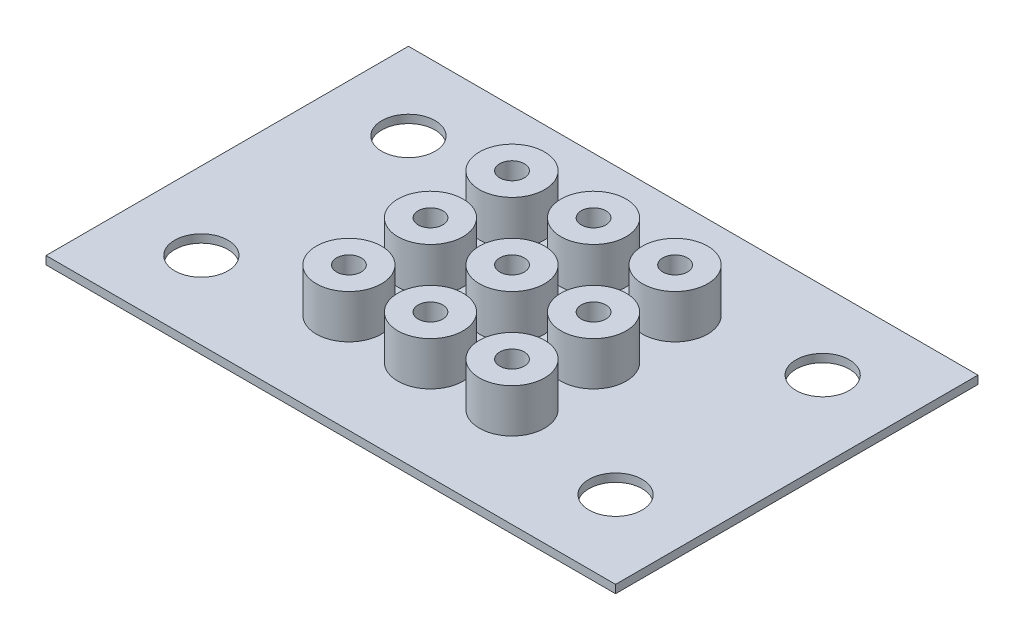
SolidWorks part; units mm, degrees
ref_plane "Front Plane" through (0, 0, 0) normal (0, 0, 1) x (1, 0, 0)
ref_plane "Top Plane" through (0, 0, 0) normal (0, 1, 0) x (1, 0, 0)
ref_plane "Right Plane" through (0, 0, 0) normal (1, 0, 0) x (0, 0, -1)
sketch "Sketch1" plane through (0, 0, 0) normal (0, 1, 0) x (1, 0, 0)
  line L0 (9.525, 34.925) -> (0, 34.925) construction
  line L1 (0, 0) -> (69.85, 0)
  line L2 (0, 0) -> (0, 44.45)
  line L3 (0, 44.45) -> (69.85, 44.45)
  line L4 (69.85, 0) -> (69.85, 44.45)
  line L5 (9.525, 34.925) -> (60.325, 34.925) construction
  line L6 (9.525, 34.925) -> (9.525, 9.525) construction
  line L7 (9.525, 9.525) -> (60.325, 9.525) construction
  line L8 (60.325, 34.925) -> (60.325, 9.525) construction
  line L9 (9.525, 34.925) -> (9.525, 44.45) construction
  line L10 (34.925, 22.225) -> (34.925, 32.225) construction
  circle A0 centre (9.525, 34.925) radius 3.2639
  circle A1 centre (60.325, 34.925) radius 3.2639
  circle A2 centre (9.525, 9.525) radius 3.2639
  circle A3 centre (60.325, 9.525) radius 3.2639
  circle A4 centre (34.925, 22.225) radius 1.25
  circle A5 centre (44.925, 22.225) radius 1.25
  circle A6 centre (44.925, 32.225) radius 1.25
  circle A7 centre (34.925, 32.225) radius 1.25
  circle A8 centre (24.925, 22.225) radius 1.25
  circle A9 centre (24.925, 32.225) radius 1.25
  circle A10 centre (34.925, 32.225) radius 1.25
  circle A11 centre (44.925, 22.225) radius 1.25
  circle A12 centre (44.925, 12.225) radius 1.25
  circle A13 centre (34.925, 12.225) radius 1.25
  circle A14 centre (24.925, 22.225) radius 1.25
  circle A15 centre (24.925, 12.225) radius 1.25
  circle A16 centre (34.925, 12.225) radius 1.25
  point P13 (34.925, 34.925)
  point P14 (34.925, 44.45)
  point P20 (69.85, 22.225)
  dimension "D5" = 6.5278
  dimension "D6" = 2.5
  dimension "D1" = 69.85
  dimension "D2" = 44.45
  dimension "D3" = 50.8
  dimension "D4" = 25.4
  dimension "D9" = 10
  dimension "D16" = 10
  dimension "D17" = 10
  dimension "D18" = 10
  dimension "D19" = 10
  dimension "D20" = 10
  dimension "D21" = 10
  dimension "D22" = 10
  dimension "D7" = 2
  dimension "D8" = 2
  dimension "D10" = 2
  dimension "D11" = 2
  dimension "D12" = 2
  dimension "D13" = 2
  dimension "D14" = 2
  dimension "D15" = 2
extrude "Boss-Extrude1" add sketch "Sketch1" along normal blind 1 contours L1 L4 L3 L2 A15 A13 A12 A9 A8 A7 A6 A5 A4 A3 A2 A1 A0 region at (0.8279, 0, -22.225)
sketch "Sketch2" plane through (0, 1, 0) normal (0, 1, 0) x (1, 0, 0)
  line L0 (34.925, 22.225) -> (34.925, 32.225) construction
  circle A0 centre (34.925, 22.225) radius 4
  circle A1 centre (34.925, 22.225) radius 1.51
  circle A2 centre (44.925, 22.225) radius 4
  circle A3 centre (44.925, 22.225) radius 1.51
  circle A4 centre (44.925, 32.225) radius 4
  circle A5 centre (44.925, 32.225) radius 1.51
  circle A6 centre (34.925, 32.225) radius 4
  circle A7 centre (34.925, 32.225) radius 1.51
  circle A8 centre (44.925, 22.225) radius 1.51
  circle A9 centre (44.925, 22.225) radius 4
  circle A10 centre (44.925, 12.225) radius 1.51
  circle A11 centre (44.925, 12.225) radius 4
  circle A12 centre (34.925, 12.225) radius 1.51
  circle A13 centre (34.925, 12.225) radius 4
  circle A14 centre (24.925, 22.225) radius 4
  circle A15 centre (24.925, 22.225) radius 1.51
  circle A16 centre (24.925, 32.225) radius 4
  circle A17 centre (24.925, 32.225) radius 1.51
  circle A18 centre (34.925, 32.225) radius 4
  circle A19 centre (34.925, 32.225) radius 1.51
  circle A20 centre (24.925, 22.225) radius 1.51
  circle A21 centre (24.925, 22.225) radius 4
  circle A22 centre (24.925, 12.225) radius 1.51
  circle A23 centre (24.925, 12.225) radius 4
  circle A24 centre (34.925, 12.225) radius 1.51
  circle A25 centre (34.925, 12.225) radius 4
  dimension "D1" = 3.02
  dimension "D2" = 8
  dimension "D5" = 10
  dimension "D10" = 10
  dimension "D11" = 10
  dimension "D12" = 10
  dimension "D13" = 10
  dimension "D14" = 10
  dimension "D15" = 10
  dimension "D16" = 10
  dimension "D3" = 2
  dimension "D4" = 2
  dimension "D6" = 2
  dimension "D7" = 2
  dimension "D8" = 2
  dimension "D9" = 2
extrude "Boss-Extrude2" add sketch "Sketch2" along normal blind 5.35 contours A16 A17 | A14 A15 | A6 A7 | A4 A5 | A2 A3 | A1 A0 | A23 A22 | A13 A12 | A11 A10 region at (31.0381, 1, -22.225) region at (41.0381, 1, -22.225) region at (41.0381, 1, -32.225) region at (31.0381, 1, -32.225) region at (41.0381, 1, -12.225) region at (31.0381, 1, -12.225) region at (21.0381, 1, -22.225) region at (21.0381, 1, -32.225) region at (21.0381, 1, -12.225)
